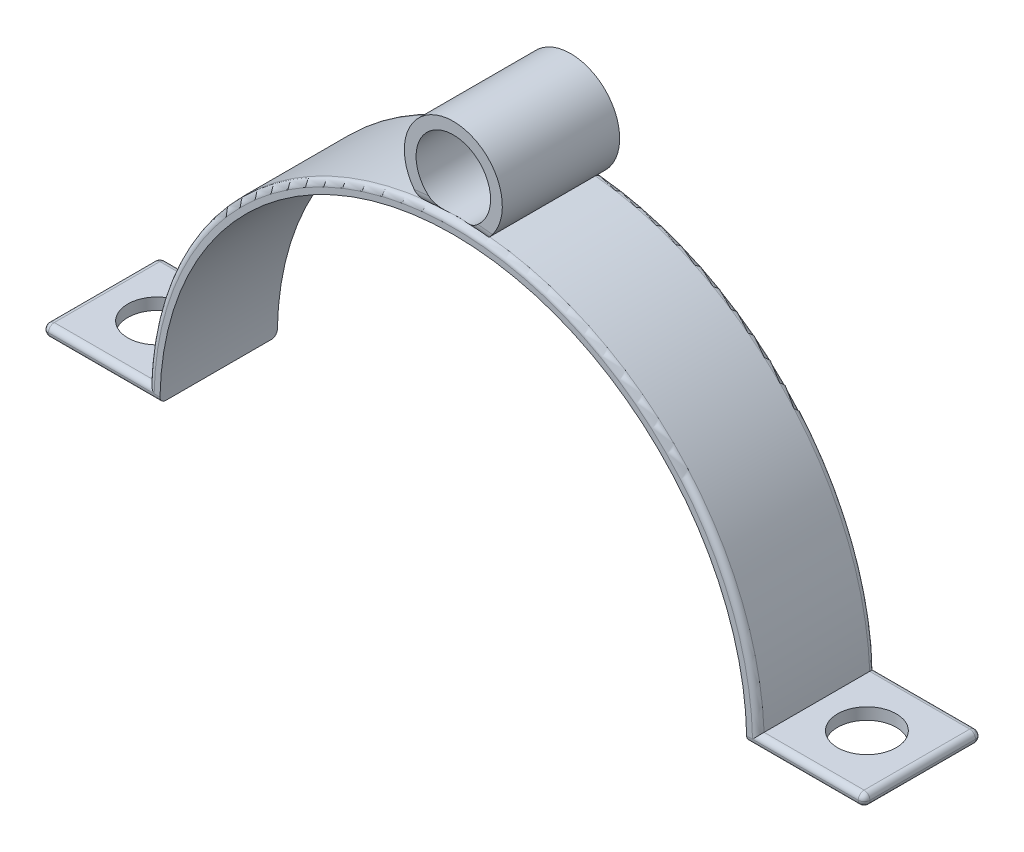
SolidWorks part; units mm, degrees
ref_plane "Front Plane" through (0, 0, 0) normal (0, 0, 1) x (1, 0, 0)
ref_plane "Top Plane" through (0, 0, 0) normal (0, 1, 0) x (1, 0, 0)
ref_plane "Right Plane" through (0, 0, 0) normal (1, 0, 0) x (0, 0, -1)
sketch "Sketch1" plane through (0, 0, 0) normal (0, 0, 1) x (1, 0, 0)
  line L0 (-50, 0) -> (-70, 0)
  line L1 (-70, 0) -> (-70, 2)
  line L2 (-70, 2) -> (-51.96, 2)
  line L4 (50, 0) -> (70, 0)
  line L5 (70, 0) -> (70, 2)
  line L6 (51.96, 2) -> (70, 2)
  arc A0 (50, 0) -> (-50, 0) centre (0, 0) ccw
  arc A1 (51.96, 2) -> (-51.96, 2) centre (0, 0) ccw
  dimension "D1" = 100
  dimension "D2" = 20
  dimension "D3" = 2
  dimension "D5" = 20
  dimension "D6" = 2
extrude "Boss-Extrude1" add sketch "Sketch1" along normal blind 20
fillet "Fillet4" radius 1 1 edges at (-70, 1, 20)
fillet "Fillet5" radius 1 1 edges at (-70, 1, 0)
fillet "Fillet7" radius 1 10 edges at (-59.5, 0, 20) (-69.7071, 0, 19.7071) (-59.5, 0, 0) (-69.7071, 0, 0.2929) (-60.48, 2, 20) (-69.7071, 2, 19.7071) (-60.48, 2, 0) (-69.7071, 2, 0.2929) (-70, 0, 10) (-70, 2, 10)
fillet "Fillet10" radius 1 2 edges at (70, 1, 20) (70, 1, 0)
fillet "Fillet11" radius 1 10 edges at (59.5, 0, 20) (69.7071, 0, 19.7071) (59.5, 0, 0) (69.7071, 0, 0.2929) (60.48, 2, 20) (69.7071, 2, 19.7071) (60.48, 2, 0) (69.7071, 2, 0.2929) (70, 0, 10) (70, 2, 10)
fillet "Fillet12" radius 1 2 edges at (0, 51.9985, 0) (0, 51.9985, 20)
sketch "Sketch2" plane through (0, 2, 0) normal (0, 1, 0) x (1, 0, 0)
  circle A0 centre (-60.48, -10) radius 5
  circle A1 centre (60.48, -10) radius 5
  dimension "D1" = 10
  dimension "D2" = 10
extrude "Cut-Extrude1" cut sketch "Sketch2" against normal through all
sketch "Sketch3" plane through (0, 0, 0) normal (0, 0, 1) x (1, 0, 0)
  arc A1 (5.1107, 51.7467) -> (-5.1107, 51.7467) centre (0, 0) ccw
  arc A4 (5.1107, 51.7467) -> (-5.1107, 51.7467) centre (0, 58.35) ccw
extrude "Boss-Extrude3" add sketch "Sketch3" along normal blind 20 contours A4 A1
sketch "Sketch4" plane through (0, 0, 20) normal (0, 0, 1) x (1, 0, 0)
  circle A0 centre (0, 58.35) radius 6.35
  dimension "D1" = 12.7
extrude "Cut-Extrude2" cut sketch "Sketch4" against normal through all
fillet "Fillet18" radius 2 1 edges at (0, 51.9985, 0)
fillet "Fillet19" radius 2 1 edges at (0, 51.9985, 20)
